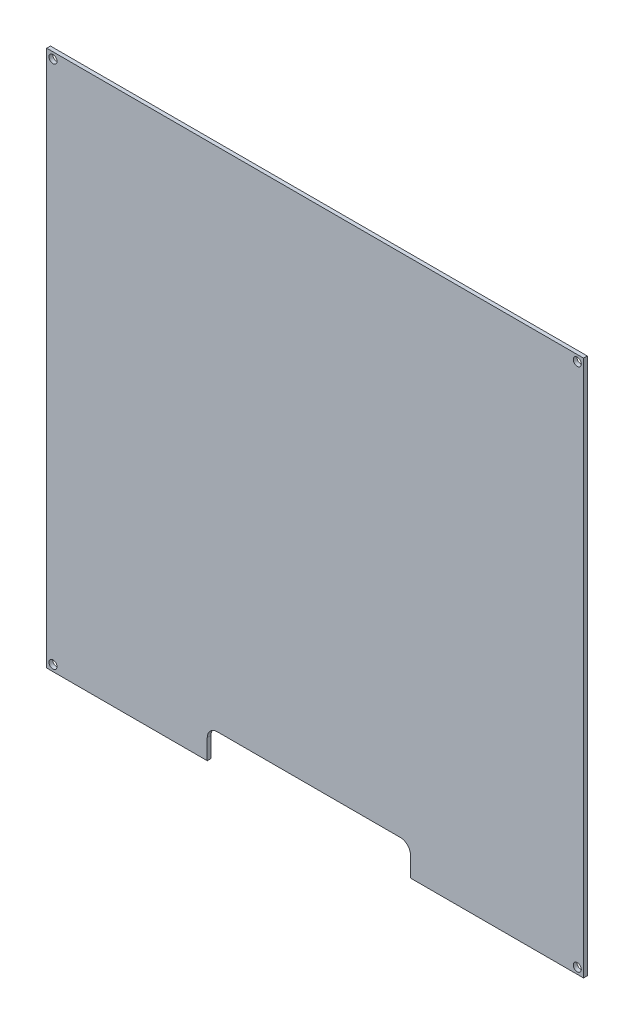
SolidWorks part; units mm, degrees
material "1060 Alloy"
ref_plane "Front Plane" through (0, 0, 0) normal (0, 0, 1) x (1, 0, 0)
ref_plane "Top Plane" through (0, 0, 0) normal (0, 1, 0) x (1, 0, 0)
ref_plane "Right Plane" through (0, 0, 0) normal (1, 0, 0) x (0, 0, -1)
sketch "Sketch1" plane through (0, 0, 0) normal (0, 0, 1) x (1, 0, 0)
  line L0 (-100, -100) -> (100, -100) construction
  line L1 (-100, -100) -> (-100, 100) construction
  line L2 (100, -100) -> (100, 100) construction
  line L3 (-100, 100) -> (100, 100) construction
  line L4 (-100, -100) -> (100, 100) construction
  line L5 (100, -100) -> (-100, 100) construction
  line L6 (-107, 0) -> (107, 0) construction
  line L7 (-107, -107) -> (107, -107)
  line L8 (-107, -107) -> (-107, 107)
  line L9 (-107, 107) -> (107, 107)
  line L10 (107, -107) -> (107, 107)
  line L11 (-107, -107) -> (107, 107) construction
  line L12 (-107, 107) -> (107, -107) construction
  circle A0 centre (-104.5, 104.5) radius 1.6
  circle A1 centre (104.5, 104.5) radius 1.6
  circle A2 centre (0, -104.5) radius 1.6
  circle A3 centre (104.5, -104.5) radius 1.6
  circle A4 centre (-104.5, -104.5) radius 1.6
  point P0 (0, 0)
  point P1 (0, 0)
  dimension "D4" = 3.2
  dimension "D1" = 209
  dimension "D2" = 200
  dimension "D3" = 214
  dimension "D5" = 209
extrude "Boss-Extrude1" add sketch "Sketch1" along normal blind 1.5
sketch "Sketch2" plane through (0, 0, 1.5) normal (0, 0, 1) x (1, 0, 0)
  line L0 (-107, -107) -> (107, -107) construction
  line L1 (-43, -107) -> (38, -107)
  line L2 (-43, -107) -> (-43, -95)
  line L3 (-43, -95) -> (38, -95)
  line L4 (38, -107) -> (38, -95)
  dimension "D1" = 12
  dimension "D2" = 43
  dimension "D3" = 81
extrude "Cut-Extrude1" cut sketch "Sketch2" against normal through all
fillet "Fillet1" radius 4 2 edges at (38, -95, 0.75) (-43, -95, 0.75)
